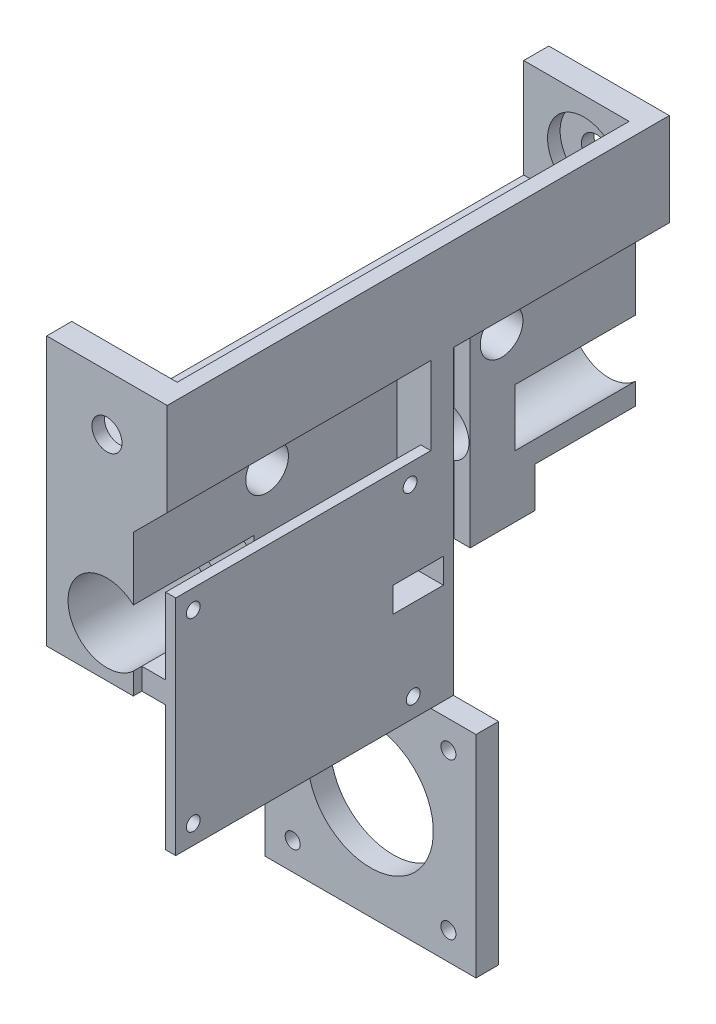
SolidWorks part; units mm, degrees
ref_plane "Front Plane" through (0, 0, 0) normal (0, 0, 1) x (1, 0, 0)
ref_plane "Top Plane" through (0, 0, 0) normal (0, 1, 0) x (1, 0, 0)
ref_plane "Right Plane" through (0, 0, 0) normal (1, 0, 0) x (0, 0, -1)
sketch "Sketch1" plane through (0, 0, 0) normal (0, 0, 1) x (1, 0, 0)
  line L0 (-12, 7) -> (9, 7)
  line L1 (-12, 26.75) -> (12, 26.75) construction
  line L2 (-12, 26.75) -> (-12, -26.75) construction
  line L3 (-12, -26.75) -> (12, -26.75)
  line L4 (12, 26.75) -> (12, -26.75)
  line L5 (-12, 26.75) -> (12, -26.75) construction
  line L6 (-12, -26.75) -> (12, 26.75) construction
  line L7 (9, 7) -> (9, 26.75)
  line L8 (9, 26.75) -> (12, 26.75)
  line L9 (-12, 7) -> (-12, -26.75)
  line L10 (-12, 7.75) -> (-12, 6.25) construction
  circle A0 centre (0, -16.75) radius 7 construction
  circle A1 centre (-12, -0.75) radius 7 construction
  circle A2 centre (-12, 15.75) radius 8 construction
  circle A3 centre (0, -16.75) radius 7.75
  point P2 (-7, -16.75)
  point P4 (0, 0)
  point P9 (0, -23.75)
  point P14 (-12, 7.75)
  point P15 (0, -9.75)
  point P16 (-12, -7.75)
  point P17 (-12, 23.75)
  dimension "D1" = 14
  dimension "D5" = 16
  dimension "D9" = 15.5
  dimension "D2" = 5
  dimension "D3" = 3
  dimension "D4" = 8.5
  dimension "D6" = 2
  dimension "D7" = 3
  dimension "D8" = 3
extrude "Boss-Extrude1" add sketch "Sketch1" along normal mid plane 100
sketch "Sketch2" plane through (-12, 0, 0) normal (-1, 0, 0) x (0, 0, 1)
  line L0 (-23.35, -0.75) -> (23.35, -0.75) construction
  circle A0 centre (-23.35, -0.75) radius 4.25
  circle A1 centre (23.35, -0.75) radius 4.25
  point P0 (0, -0.75)
  dimension "D2" = 8.5
  dimension "D1" = 46.7
extrude "Cut-Extrude1" cut sketch "Sketch2" against normal through all
sketch "Sketch3" plane through (9, 0, 0) normal (-1, 0, 0) x (0, 0, 1)
  line L0 (50, 7) -> (-50, 7) construction
  line L1 (-50, 26.75) -> (-45, 26.75)
  line L2 (-50, 26.75) -> (-50, 7)
  line L3 (-50, 7) -> (-45, 7)
  line L4 (-45, 26.75) -> (-45, 7)
  line L6 (50, 26.75) -> (45, 26.75)
  line L7 (50, 26.75) -> (50, 7)
  line L8 (50, 7) -> (45, 7)
  line L9 (45, 26.75) -> (45, 7)
  dimension "D1" = 5
extrude "Boss-Extrude2" add sketch "Sketch3" along normal through all
sketch "Sketch4" plane through (0, 0, 0) normal (0, 0, 1) x (1, 0, 0)
  circle A0 centre (0, 15.75) radius 7.25
  dimension "D1" = 14.5
extrude "Cut-Extrude4" cut sketch "Sketch4" against normal mid plane 95
sketch "Sketch6" plane through (0, 0, 0) normal (0, 0, 1) x (1, 0, 0)
  circle A0 centre (0, -16.75) radius 5
  circle A3 centre (0, -16.75) radius 7.75 construction
  circle A4 centre (0, -16.75) radius 7.75
  dimension "D1" = 10
extrude "Boss-Extrude3" add sketch "Sketch6" along normal mid plane 52
sketch "Sketch7" plane through (-12, 0, 0) normal (-1, 0, 0) x (0, 0, 1)
  line L0 (-35, -16.75) -> (35, -16.75) construction
  circle A0 centre (-35, -16.75) radius 1
  circle A1 centre (35, -16.75) radius 1
  dimension "D1" = 2
  dimension "D2" = 70
extrude "Cut-Extrude5" cut sketch "Sketch7" against normal up to next
sketch "Sketch8" plane through (0, 0, 47.5) normal (0, 0, -1) x (-1, 0, 0)
  circle A0 centre (0, 15.75) radius 3
  dimension "D1" = 6
extrude "Cut-Extrude6" cut sketch "Sketch8" against normal through all both and the other way through all
sketch "Sketch9" plane through (0, 0, 50) normal (0, 0, 1) x (1, 0, 0)
  line L0 (5.25, 1.5) -> (12, 8.25)
  line L1 (12, -26.75) -> (5.25, -26.75)
  line L2 (12, -26.75) -> (12, 8.25)
  line L4 (5.25, -26.75) -> (5.25, 1.5)
  circle A2 centre (0, -16.75) radius 7.75 construction
  circle A3 centre (0, -16.75) radius 7.75 construction
  point P5 (7.75, -16.75)
  dimension "D1" = 2.5
  dimension "D2" = 35
  dimension "D3" = 45
extrude "Cut-Extrude7" cut sketch "Sketch9" against normal through all
sketch "Sketch10" plane through (-12, 0, 0) normal (-1, 0, 0) x (0, 0, 1)
  line L0 (-5, -26.75) -> (-5, -31.75)
  line L1 (50, -26.75) -> (-50, -26.75) construction
  line L2 (-5, -31.75) -> (5, -31.75)
  line L3 (5, -31.75) -> (5, -26.75)
  line L4 (5, -26.75) -> (30, -26.75)
  line L5 (30, -26.75) -> (30, -34.75)
  line L6 (30, -34.75) -> (-30, -34.75)
  line L7 (-30, -34.75) -> (-30, -26.75)
  line L8 (-30, -26.75) -> (-5, -26.75)
  line L9 (-50, 26.75) -> (-50, -26.75) construction
  point P15 (0, -31.75)
  dimension "D1" = 5
  dimension "D2" = 3
  dimension "D3" = 10
  dimension "D4" = 20
extrude "Boss-Extrude4" add sketch "Sketch10" against normal up to surface (17.25 mm away) up to face at (5.25, -11.9687, 0)
sketch "Sketch11" plane through (0, -31.75, 0) normal (0, 1, 0) x (1, 0, 0)
  line L0 (-1.25, 2.5) -> (-12, 2.5)
  line L1 (-12, -5) -> (-12, 5) construction
  line L2 (-12, 2.5) -> (-12, -2.5)
  line L3 (-12, -2.5) -> (-1.25, -2.5)
  line L4 (-7.75, -26) -> (5.25, -26) construction
  line L6 (-7.75, -26) -> (5.25, -26) construction
  arc A0 (-1.25, 2.5) -> (-1.25, -2.5) centre (-1.25, 0) cw
  point P10 (-1.25, -26)
  dimension "D1" = 5
extrude "Cut-Extrude8" cut sketch "Sketch11" against normal through all
sketch "Sketch21" plane through (0, 7, 0) normal (0, 1, 0) x (1, 0, 0)
  line L0 (-12, 27.6) -> (-12, 19.1) construction
  line L1 (-12, 27.6) -> (-12, 19.1) construction
  line L2 (-12, -19.1) -> (-12, -27.6) construction
  line L3 (-12, -19.1) -> (-12, -27.6) construction
  circle A0 centre (-7, 23.35) radius 1
  circle A1 centre (-7, -23.35) radius 1
  point P9 (-12, 23.35)
  point P10 (-12, -23.35)
  dimension "D1" = 2
  dimension "D2" = 5
extrude "Cut-Extrude11" cut sketch "Sketch21" against normal up to next
sketch "Sketch12" plane through (0, 7, 0) normal (0, 1, 0) x (1, 0, 0)
  line L0 (2, 12.05) -> (-2, 12.05) construction
  line L1 (2, 17.1) -> (7, 17.1)
  line L2 (2, 17.1) -> (2, 7)
  line L3 (2, 7) -> (7, 7)
  line L4 (7, 17.1) -> (7, 7)
  line L5 (-2, 17.1) -> (-7, 17.1)
  line L6 (-2, 17.1) -> (-2, 7)
  line L7 (-2, 7) -> (-7, 7)
  line L8 (-7, 17.1) -> (-7, 7)
  line L10 (5.25, 5) -> (-12, 5) construction
  line L11 (5.25, 19.1) -> (5.25, 27.6) construction
  line L12 (5.25, 19.1) -> (5.25, 27.6) construction
  point P10 (0, 12.05)
  dimension "D1" = 2
  dimension "D2" = 2
  dimension "D3" = 4
  dimension "D4" = 14
extrude "Cut-Extrude9" cut sketch "Sketch12" against normal through all
sketch "Sketch13" plane through (0, -34.75, 0) normal (0, -1, 0) x (1, 0, 0)
  line L12 (5.25, -7) -> (12, -7)
  line L13 (12, -50) -> (12, 50) construction
  line L14 (12, -7) -> (12, -2.5)
  line L15 (12, -2.5) -> (5.25, -2.5)
  line L16 (5.25, 30) -> (5.25, -7) construction
  line L17 (5.25, -2.5) -> (5.25, -7)
  line L18 (-1.25, -2.5) -> (-12, -2.5) construction
extrude "Boss-Extrude5" add sketch "Sketch13" against normal up to next
sketch "Sketch14" plane through (5.25, 0, 0) normal (-1, 0, 0) x (0, 0, 1)
  line L4 (-2.5, -26.75) -> (-5, -26.75)
  line L5 (-5, -26.75) -> (-5, -31.75)
  line L6 (-5, -31.75) -> (-2.5, -31.75)
  line L7 (-2.5, -31.75) -> (-2.5, -26.75)
  line L12 (-2.5, -26.75) -> (-5, -26.75)
  line L13 (-5, -26.75) -> (-5, -31.75)
  line L14 (-5, -31.75) -> (-2.5, -31.75)
  line L15 (-2.5, -31.75) -> (-2.5, -26.75)
  dimension "D1" = 0
extrude "Cut-Extrude10" cut sketch "Sketch14" against normal through all
sketch "Sketch16" plane through (0, 0, -7) normal (0, 0, -1) x (-1, 0, 0)
  line L0 (-12, -34.75) -> (-5, -34.75)
  line L1 (-2, -34.75) -> (-12, -34.75) construction
  line L2 (-5, -34.75) -> (-5, -49.75)
  line L3 (-5, -49.75) -> (5, -49.75)
  line L4 (5, -49.75) -> (5, -34.75)
  line L5 (-5.25, -34.75) -> (12, -34.75) construction
  line L6 (5, -34.75) -> (12, -34.75)
  line L7 (12, -34.75) -> (12, -51.75)
  line L9 (-12, -51.75) -> (-12, -34.75)
  line L10 (-12, -51.75) -> (-21, -51.75)
  line L11 (-21, -51.75) -> (-21, -93.75)
  line L12 (-21, -93.75) -> (21, -93.75)
  line L13 (21, -93.75) -> (21, -51.75)
  line L14 (21, -51.75) -> (12, -51.75)
  line L16 (-15.5, -88.25) -> (15.5, -88.25) construction
  line L17 (-15.5, -88.25) -> (-15.5, -57.25) construction
  line L18 (-15.5, -57.25) -> (15.5, -57.25) construction
  line L19 (15.5, -88.25) -> (15.5, -57.25) construction
  line L20 (-15.5, -88.25) -> (15.5, -57.25) construction
  line L21 (-15.5, -57.25) -> (15.5, -88.25) construction
  circle A0 centre (0, -72.75) radius 12.5
  circle A1 centre (-15.5, -57.25) radius 1.5
  circle A2 centre (15.5, -57.25) radius 1.5
  circle A3 centre (15.5, -88.25) radius 1.5
  circle A4 centre (-15.5, -88.25) radius 1.5
  point P20 (-21, -72.75)
  point P21 (0, -93.75)
  dimension "D5" = 25
  dimension "D7" = 3
  dimension "D1" = 10
  dimension "D2" = 15
  dimension "D3" = 2
  dimension "D4" = 42
  dimension "D6" = 31
extrude "Boss-Extrude8" add sketch "Sketch16" against normal up to surface (4.5 mm away) up to face at (8.625, -10.9375, -2.5)
sketch "Sketch18" plane through (12, 0, 0) normal (1, 0, 0) x (0, 0, -1)
  line L0 (2.5, -51.75) -> (-48.3, -51.75)
  line L1 (2.5, -51.75) -> (2.5, -31.75)
  line L2 (2.5, -31.75) -> (-5, -31.75)
  line L3 (-5, -31.75) -> (-5, -26.75)
  line L4 (-5, -26.75) -> (2.5, -26.75)
  line L5 (2.5, -26.75) -> (2.5, -7.3)
  line L6 (2.5, 1.5) -> (2.5, -26.75) construction
  line L7 (2.5, -7.3) -> (-48.3, -7.3)
  line L8 (-48.3, -7.3) -> (-48.3, -51.75)
  line L10 (-44.81, -47.94) -> (-0.99, -47.94) construction
  line L11 (-44.81, -47.94) -> (-44.81, -11.11) construction
  line L12 (-44.81, -11.11) -> (-0.99, -11.11) construction
  line L13 (-0.99, -47.94) -> (-0.99, -11.11) construction
  line L14 (-44.81, -47.94) -> (-0.99, -11.11) construction
  line L15 (-44.81, -11.11) -> (-0.99, -47.94) construction
  circle A0 centre (-44.81, -11.11) radius 1.375
  circle A2 centre (-0.99, -47.94) radius 1.375
  circle A3 centre (-44.81, -47.94) radius 1.375
  circle A4 centre (-1.63, -11.11) radius 1.375
  point P15 (-22.9, -29.525)
  point P21 (-48.3, -29.525)
  point P23 (-22.9, -51.75)
  dimension "D5" = 2.75
  dimension "D1" = 50.8
  dimension "D2" = 44.45
  dimension "D3" = 43.82
  dimension "D4" = 36.83
  dimension "D6" = 0.64
extrude "Boss-Extrude9" add sketch "Sketch18" against normal blind 2
sketch "Sketch20" plane through (10, 0, 0) normal (-1, 0, 0) x (0, 0, 1)
  line L0 (-2.5, -31.75) -> (-2.5, -34.75)
  line L1 (-2.5, -51.75) -> (-2.5, -31.75) construction
  line L3 (48.3, -7.3) -> (48.3, -51.75) construction
  line L5 (48.3, -22.4509) -> (-2.5, -22.4509)
  line L6 (-2.5, -22.4509) -> (-2.5, -26.75)
  line L7 (-2.5, -26.75) -> (5, -26.75)
  line L8 (5, -26.75) -> (5, -31.75)
  line L9 (5, -31.75) -> (-2.5, -31.75)
  line L10 (48.3, -22.4509) -> (48.3, -26.75)
  line L11 (48.3, -26.75) -> (30, -26.75)
  line L12 (30, -26.75) -> (30, -34.75)
  line L13 (30, -34.75) -> (-2.5, -34.75)
  line L14 (26, -22.4509) -> (50, -22.4509) construction
extrude "Boss-Extrude10" add sketch "Sketch20" along normal up to next
